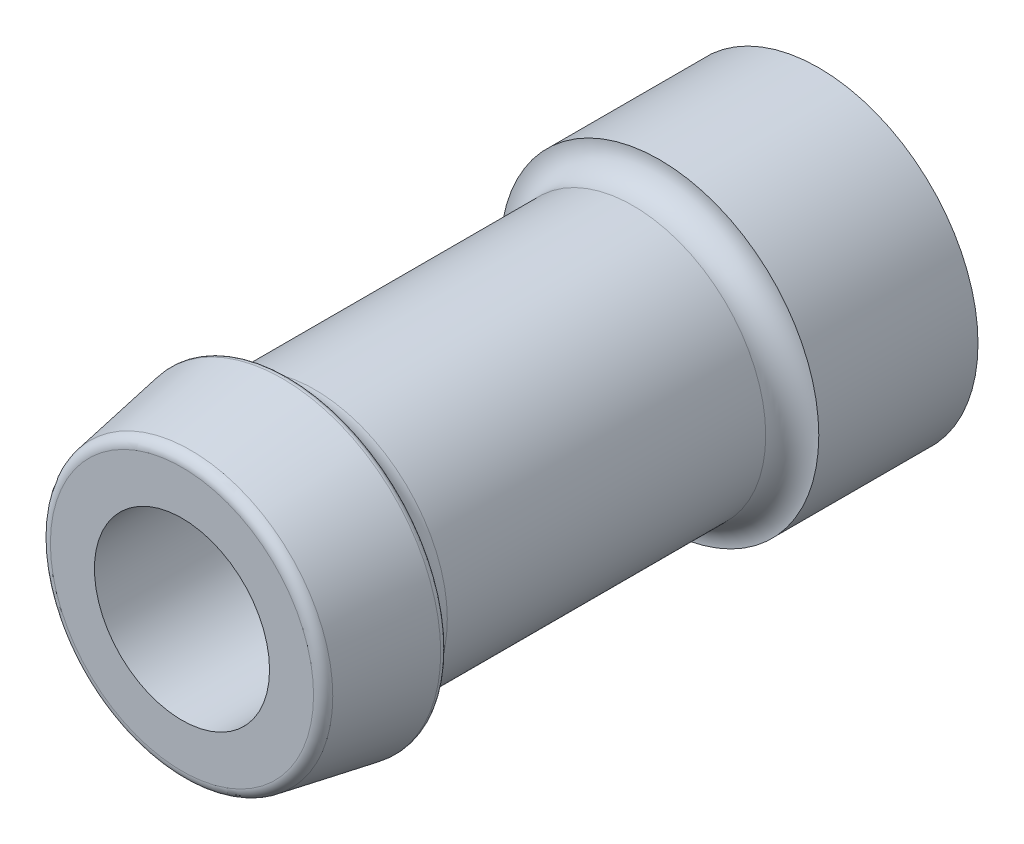
SolidWorks part; units mm, degrees
material "Custom Plastic"
ref_plane "X-Y Datum" through (0, 0, 0) normal (0, 0, 1) x (1, 0, 0)
ref_plane "X-Z Datum" through (0, 0, 0) normal (0, 1, 0) x (1, 0, 0)
ref_plane "Y-Z Datum" through (0, 0, 0) normal (1, 0, 0) x (0, 0, -1)
sketch "Sketch1" plane through (0, 0, 0) normal (0, 0, 1) x (1, 0, 0)
  circle A0 centre (0, 0) radius 7.62
  dimension "D1" = 15.24
extrude "Boss-Extrude1" add sketch "Sketch1" along normal blind 30.48
sketch "Sketch2" plane through (0, 0, 30.48) normal (0, 0, 1) x (1, 0, 0)
  circle A0 centre (0, 0) radius 4.191
  dimension "D1" = 8.382
extrude "Cut-Extrude1" cut sketch "Sketch2" against normal blind 30.48
sketch "Sketch3" plane through (0, 0, 30.48) normal (0, 0, 1) x (1, 0, 0)
  circle A0 centre (0, 0) radius 6.35
  circle A1 centre (0, 0) radius 10.16
  dimension "D1" = 12.7
  dimension "D2" = 20.32
extrude "Cut-Extrude2" cut sketch "Sketch3" against normal blind 17.78 from offset 5.08 offset against normal yes
fillet "Fillet1" radius 1.27 1 edges at (6.35, 0, 7.62)
fillet "Fillet2" radius 1.27 1 edges at (6.35, 0, 25.4)
chamfer "Chamfer1" distance 5.08 angle 10 1 edges at (7.62, 0, 30.48) first distance on face at (7.62, 0, 25.4)
fillet "Fillet3" radius 0.508 1 edges at (6.7243, 0, 30.48)
fillet "Fillet4" radius 0.254 1 edges at (7.62, 0, 25.4)
